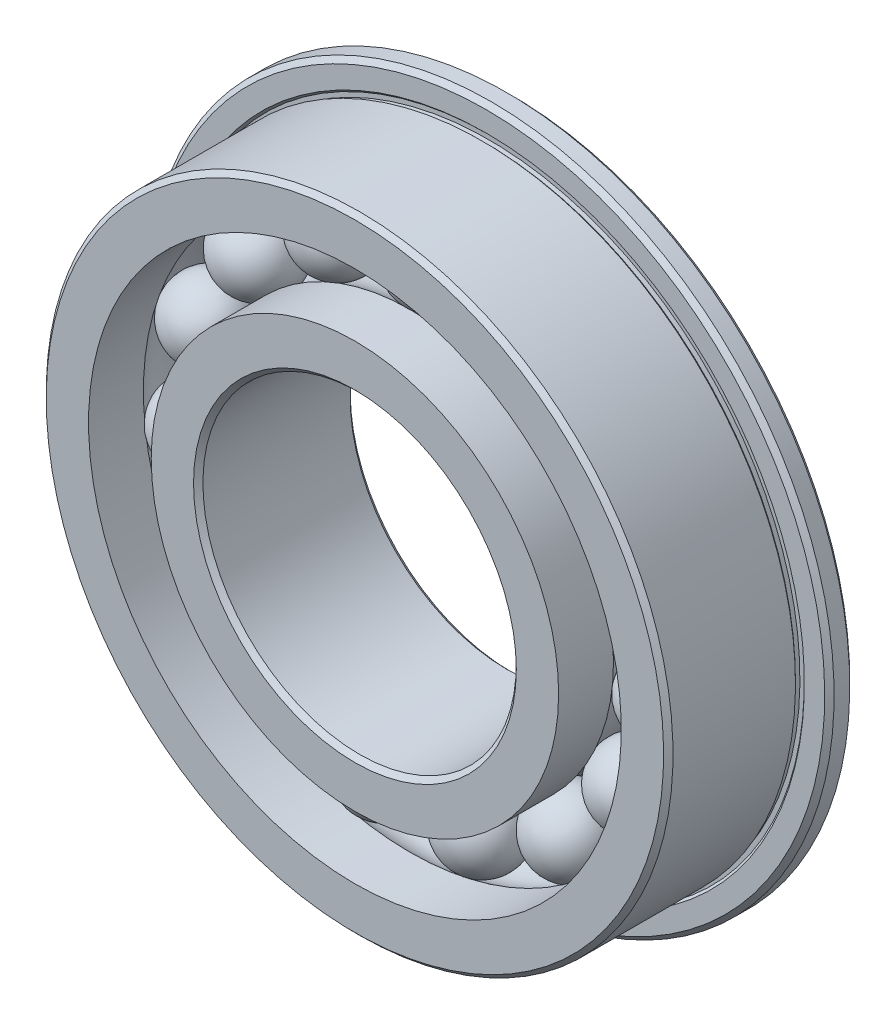
SolidWorks part; units mm, degrees
ref_plane "Front Plane" through (0, 0, 0) normal (0, 0, 1) x (1, 0, 0)
ref_plane "Top Plane" through (0, 0, 0) normal (0, 1, 0) x (1, 0, 0)
ref_plane "Right Plane" through (0, 0, 0) normal (1, 0, 0) x (0, 0, -1)
sketch "Sketch1" plane through (0, 0, 0) normal (1, 0, 0) x (0, 0, -1)
  line L0 (0, 6.35) -> (0, -6.35) construction
  line L1 (-1.5875, 6.35) -> (1.5875, 6.35) construction
  line L2 (0, 0) -> (1.5875, 0) construction
  line L3 (1.5875, 6.9469) -> (1.5875, -6.9469) construction
  line L4 (1.5875, -6.9469) -> (1.0795, -6.9469) construction
  line L5 (1.5875, 3.175) -> (0, 3.175) construction
  line L6 (1.5875, 3.175) -> (1.5875, -3.175) construction
  dimension "OD" = 12.7
  dimension "Width" = 3.175
  dimension "Flange Dia." = 13.8938
  dimension "Flange Thickness" = 0.508
  dimension "ID" = 6.35
sketch "Sketch2" plane through (0, 0, 0) normal (1, 0, 0) x (0, 0, -1)
  line L0 (1.5875, 6.9469) -> (1.0795, 6.9469)
  line L1 (1.0795, 6.9469) -> (1.0795, 6.4398)
  line L2 (0.9897, 6.35) -> (-1.5875, 6.35)
  line L3 (-1.5875, 6.35) -> (-1.5875, 5.3975)
  line L4 (-1.5875, 5.3975) -> (-0.4762, 5.3975)
  line L5 (1.5875, 6.9469) -> (1.5875, -6.9469) construction
  line L6 (1.5875, 5.3975) -> (1.5875, 6.9469)
  line L7 (1.5875, 3.175) -> (-1.5875, 3.175)
  line L8 (-1.5875, 3.175) -> (-1.5875, 4.1275)
  line L9 (-1.5875, 4.1275) -> (-0.4762, 4.1275)
  line L10 (1.5875, 4.1275) -> (1.5875, 3.175)
  line L11 (0, 6.35) -> (0, 3.175) construction
  line L12 (-0.7937, 4.7625) -> (0.7937, 4.7625) construction
  line L13 (0.4762, 5.3975) -> (1.5875, 5.3975)
  line L14 (0.4762, 4.1275) -> (1.5875, 4.1275)
  line L15 (1.0795, 6.4398) -> (1.1244, 6.3949)
  line L16 (1.1244, 6.3949) -> (1.1244, 6.3051)
  line L17 (1.1244, 6.3051) -> (1.0346, 6.3051)
  line L18 (1.0346, 6.3051) -> (0.9897, 6.35)
  line L19 (1.0795, 6.35) -> (1.1244, 6.3051) construction
  line L20 (1.1244, 6.3949) -> (1.0346, 6.3051) construction
  line L21 (0.9897, 6.35) -> (1.0795, 6.35) construction
  line L22 (1.0795, 6.35) -> (1.0795, 6.4398) construction
  circle A0 centre (0, 4.7625) radius 0.7938 construction
  arc A1 (-0.4762, 5.3975) -> (0.4762, 5.3975) centre (0, 4.7625) cw
  arc A2 (-0.4762, 4.1275) -> (0.4762, 4.1275) centre (0, 4.7625) ccw
  dimension "D1" = 3.175
  dimension "Ball Dia." = 1.5875
  dimension "D2" = 135
  dimension "D3" = 0.127
  dimension "D4" = 1.27
  dimension "Race Thickness" = 0.9525
revolve "Revolve1" add sketch "Sketch2" angle 360 about L2
fillet "Fillet1" radius 0.0953 3 edges at (0, -6.9469, -1.5875) (0, -6.9469, -1.0795) (0, -6.35, 1.5875) profile chamfer
sketch "Sketch3" plane through (0, 0, 0) normal (0, 0, 1) x (1, 0, 0)
  line L0 (-3.175, 0) -> (3.175, 0) construction
  line L1 (-6.35, 0) -> (6.35, 0) construction
  point P5 (0, 0)
  dimension "ID2" = 6.35
  dimension "OD2" = 12.7
fillet "Fillet2" radius 0.0953 2 edges at (0, -3.175, -1.5875) (0, -3.175, 1.5875) profile chamfer
sketch "Sketch7" plane through (0, 0, 0) normal (0, 0, 1) x (1, 0, 0)
  line L0 (0, 5.5562) -> (0, 3.9687)
  line L1 (0, 6.9469) -> (0, -6.9469) construction
  line L2 (-0.9392, 5.5563) -> (0, 0) construction
  line L3 (0, 0) -> (0.9392, 5.5563) construction
  line L4 (0.9392, 5.5563) -> (-0.9392, 5.5563) construction
  circle A0 centre (0, 4.7625) radius 0.7938 construction
  circle A1 centre (0, 0) radius 5.5562 construction
  circle A2 centre (0, 0) radius 3.9687 construction
  arc A4 (0, 5.5562) -> (0, 3.9687) centre (0, 4.7625) ccw
  dimension "D1" = 19.188
revolve "Revolve3" add sketch "Sketch7" angle 360 about L0
pattern_circular "CirPattern3" count 15 over 360 about axis through (0, 0, 0) along (0, 0, -1) of bodies 107
sketch "Sketch8" [suppressed] plane through (0, 0, 0) normal (1, 0, 0) x (0, 0, -1)
  line L1 (-1.1906, 2.0241) -> (-1.0477, 2.0241)
  line L2 (-1.1906, 2.0241) -> (-1.1906, 2.1431)
  line L3 (-1.1906, 2.1431) -> (-1.0477, 2.1431)
  line L4 (-1.0477, 2.0241) -> (-1.0477, 2.1431)
  line L5 (1.1906, 2.0241) -> (1.0478, 2.0241)
  line L6 (1.1906, 2.0241) -> (1.1906, 2.1431)
  line L7 (1.1906, 2.1431) -> (1.0478, 2.1431)
  line L8 (1.0478, 2.0241) -> (1.0478, 2.1431)
  line L9 (1.1906, 1.5478) -> (1.0478, 1.5478)
  line L10 (1.1906, 1.5478) -> (1.1906, 1.4287)
  line L11 (1.1906, 1.4287) -> (1.0478, 1.4287)
  line L12 (1.0478, 1.5478) -> (1.0478, 1.4287)
  line L13 (-1.1906, 1.5478) -> (-1.0477, 1.5478)
  line L14 (-1.1906, 1.5478) -> (-1.1906, 1.4287)
  line L15 (-1.1906, 1.4287) -> (-1.0477, 1.4287)
  line L16 (-1.0477, 1.5478) -> (-1.0477, 1.4287)
  dimension "D1" = 0.3175
  dimension "D2" = 0.381
revolve "Cut-Revolve1" [suppressed] cut sketch "Sketch8" angle 360 about L2
sketch "Sketch9" [suppressed] plane through (0, 0, 0) normal (1, 0, 0) x (0, 0, -1)
  line L0 (-1.0477, 2.1431) -> (-1.0477, 1.8657)
  line L1 (-1.0477, 1.8657) -> (-1.1192, 1.7419)
  line L2 (-1.1192, 1.7419) -> (-1.1192, 1.4645)
  line L3 (1.1192, 1.4645) -> (1.1192, 1.4287) construction
  line L4 (1.0478, 2.1431) -> (1.0478, 1.8657)
  line L5 (1.0478, 1.8657) -> (1.1192, 1.7419)
  line L6 (1.1192, 1.7419) -> (1.1192, 1.4645)
  line L7 (1.1906, 1.4287) -> (1.0478, 1.4287) construction
  line L8 (-1.0835, 2.1431) -> (-1.0835, 1.8752)
  line L9 (-1.0835, 1.8752) -> (-1.1549, 1.7515)
  line L10 (-1.1549, 1.7515) -> (-1.1549, 1.4645)
  line L11 (-1.0477, 2.1431) -> (-1.0835, 2.1431)
  line L12 (-1.1192, 1.4645) -> (-1.1549, 1.4645)
  line L13 (1.0835, 2.1431) -> (1.0835, 1.8752)
  line L14 (1.0835, 1.8752) -> (1.1549, 1.7515)
  line L15 (1.1549, 1.7515) -> (1.1549, 1.4645)
  line L16 (1.0478, 2.1431) -> (1.0835, 2.1431)
  line L17 (1.1192, 1.4645) -> (1.1549, 1.4645)
  line L18 (-1.0477, 1.8657) -> (-1.0477, 2.6) construction
  line L19 (1.0478, 1.8657) -> (1.0478, 2.1431) construction
  line L20 (-1.0477, 1.4287) -> (-1.1906, 1.4287) construction
  line L22 (-1.1192, 1.4645) -> (-1.1192, 1.4287) construction
  dimension "D2" = 150
  dimension "D1" = 150
  dimension "D5" = 0.1429
  dimension "D3" = 0.0357
  dimension "D4" = 0.0357
revolve "Revolve4" [suppressed] add sketch "Sketch9" angle 360 about L2
ref_axis "Center Axis 1" through (0, 0, -0.8731) along (0, 0, 1)
ref_plane "Contact Plane 1" through (0, 0, -1.0795) normal (0, 0, 1) x (1, 0, 0)
equation "\"Ball Dia.@Sketch2\"=\"D1@Sketch2\"*.5"
equation "\"D3@Sketch2\"=\"Flange Thickness@Sketch1\"/4"
equation "\"D1@Fillet1\"=\"Race Thickness@Sketch2\"/10"
equation "\"ID2@Sketch3\" = \"ID@Sketch1\""
equation "\"OD2@Sketch3\" = \"OD@Sketch1\""
equation "\"D1@Fillet2\"=\"Race Thickness@Sketch2\"/10"
equation "\"D1@CirPattern3\"=360/\"D1@Sketch7\"-4"
equation "\"D1@Sketch8\"=\"Race Thickness@Sketch2\"/3"
equation "\"D2@Sketch8\"=\"Race Thickness@Sketch2\"/2.5"
equation "\"D3@Sketch9\"=\"D5@Sketch9\"/4"
equation "\"D4@Sketch9\"=\"D5@Sketch9\"/4"
equation "\"D1@Sketch9\"=\"D2@Sketch9\""
equation "\"D4@Sketch2\"=\"D1@Sketch2\"*.4"
